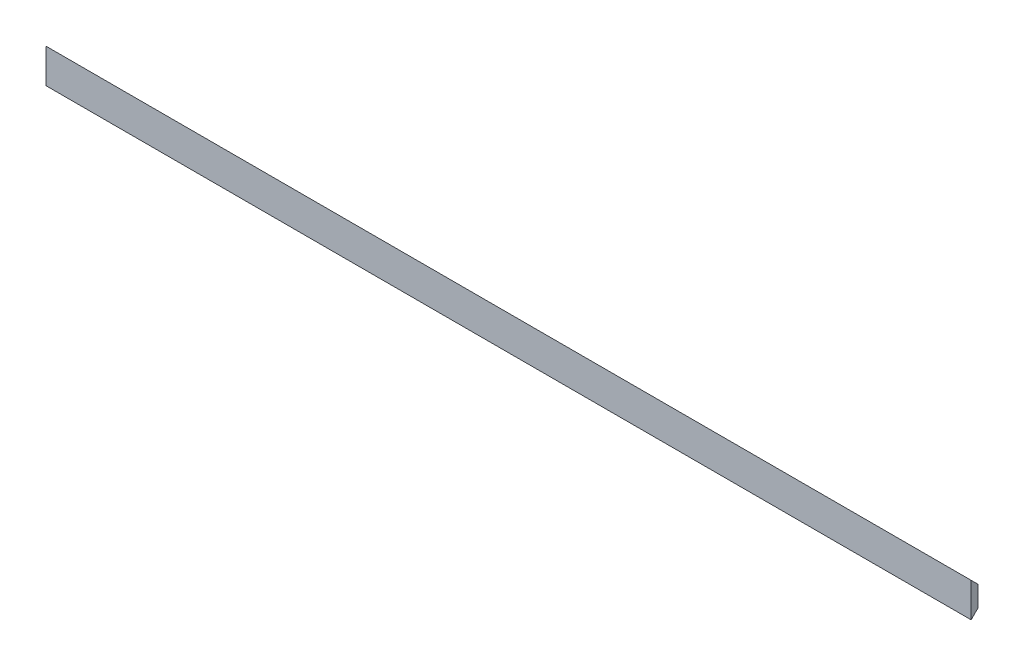
SolidWorks part; units mm, degrees
ref_plane "Plano frontal" through (0, 0, 0) normal (0, 0, 1) x (1, 0, 0)
ref_plane "Plano superior" through (0, 0, 0) normal (0, 1, 0) x (1, 0, 0)
ref_plane "Plano direito" through (0, 0, 0) normal (1, 0, 0) x (0, 0, -1)
sketch "Esboço2" plane through (0, 0, 0) normal (0, 0, 1) x (1, 0, 0)
  line L1 (0, 0) -> (2700, 0)
  line L2 (0, 0) -> (0, 100)
  line L3 (0, 100) -> (2700, 100)
  line L4 (2700, 0) -> (2700, 100)
  dimension "D1" = 2700
  dimension "D2" = 100
extrude "Ressalto-extrusão1" add sketch "Esboço2" along normal blind 20
chamfer "Chanfro1" distance 20 angle 45 2 edges at (1350, 0, 0) (1350, 100, 0)
